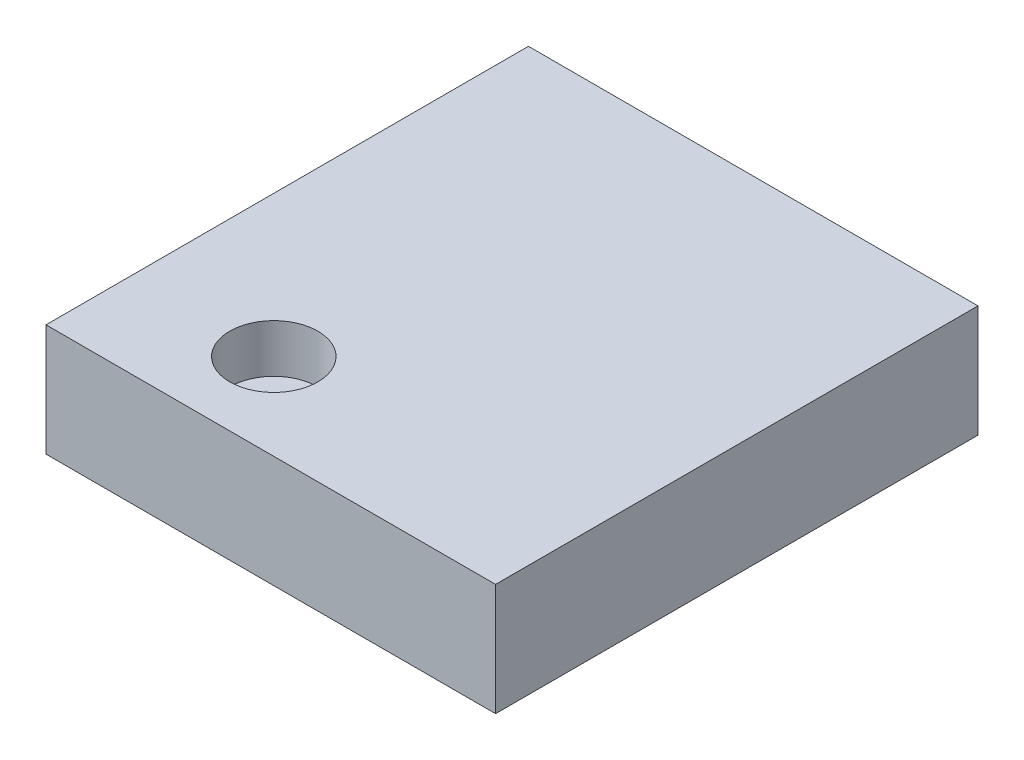
SolidWorks part; units mm, degrees
ref_plane "Front Plane" through (0, 0, 0) normal (0, 0, 1) x (1, 0, 0)
ref_plane "Top Plane" through (0, 0, 0) normal (0, 1, 0) x (1, 0, 0)
ref_plane "Right Plane" through (0, 0, 0) normal (1, 0, 0) x (0, 0, -1)
sketch "Sketch1" plane through (0, 0, 0) normal (0, 0, 1) x (1, 0, 0)
  line L1 (0, 0) -> (93.1875, 0)
  line L2 (0, 0) -> (0, 23.216)
  line L3 (0, 23.216) -> (93.1875, 23.216)
  line L4 (93.1875, 0) -> (93.1875, 23.216)
extrude "Boss-Extrude1" add sketch "Sketch1" along normal blind 100
sketch "Sketch2" plane through (0, 23.216, 0) normal (0, 1, 0) x (1, 0, 0)
  circle A0 centre (29.3018, -82.0799) radius 9.1245
extrude "Cut-Extrude1" cut sketch "Sketch2" against normal blind 10
